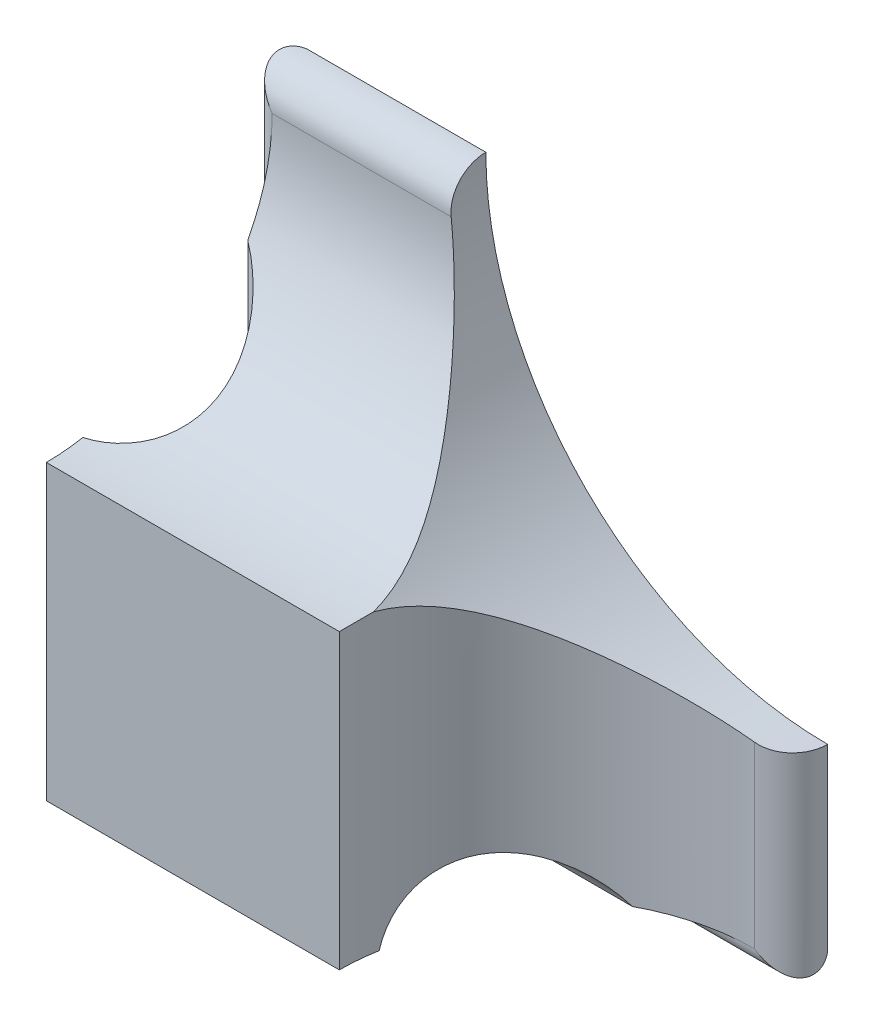
SolidWorks part; units mm, degrees
material "Золото без примесей"
ref_plane "Front" through (0, 0, 0) normal (0, 0, 1) x (1, 0, 0)
ref_plane "Top" through (0, 0, 0) normal (0, 1, 0) x (1, 0, 0)
ref_plane "Right" through (0, 0, 0) normal (1, 0, 0) x (0, 0, -1)
sketch "Эскиз1" plane through (0, 0, 0) normal (0, 0, 1) x (1, 0, 0)
  line L0 (0, 0) -> (22, 0)
  line L1 (22, 0) -> (22, 8)
  line L2 (0, 0) -> (19.7111, 19.7111) construction
  line L4 (12.1005, 12.1005) -> (0, 0)
  line L5 (22, 8) -> (22.8779, 8) construction
  line L6 (12.1005, 12.1005) -> (8.2773, 15.9237) construction
  arc A0 (22, 8) -> (12.1005, 12.1005) centre (22, 22) cw
  dimension "D1" = 45
  dimension "D2" = 8
  dimension "D3" = 22
extrude "Основная форма" add sketch "Эскиз1" along normal blind 10
sketch "Эскиз2" plane through (22, 0, 0) normal (1, 0, 0) x (0, 0, -1)
  line L1 (-10, -1) -> (0, -1)
  line L2 (0, 0.75) -> (0, -1)
  line L5 (-10, 0) -> (0, 0) construction
  line L6 (-10, 0) -> (-10, -1)
  line L8 (-10, 0) -> (-8.5, 0)
  line L10 (-1.5, 0.75) -> (-2.5, 0.75)
  line L11 (0, 0) -> (0, 8) construction
  line L12 (-10.4143, 2.5) -> (-4.9819, 2.5) construction
  arc A3 (-8.5, 0) -> (-2.5, 0.75) centre (-5.3634, -0.7176) cw
  arc A4 (0, 0.75) -> (-1.5, 0.75) centre (-0.75, 0.75) cw
  dimension "D1" = 2.5
  dimension "D2" = 1
  dimension "D3" = 1.5
  dimension "D5" = 1
  dimension "D7" = 1.5
extrude "Вырез фигурный, фронт" cut sketch "Эскиз2" against normal through all
sketch "Эскиз3" plane through (0, 0, 0) normal (0, 1, 0) x (1, 0, 0)
  line L4 (22, 0) -> (22, -10)
  line L6 (22, -10) -> (12, -10)
  line L9 (0, -10) -> (22, -10) construction
  line L10 (0.75, -1.5) -> (22, -1.5) construction
  line L11 (20.5, -10) -> (20.5, -1.5) construction
  arc A4 (12, -10) -> (20.5, -1.5) centre (20.5, -10) cw
  arc A5 (20.5, -1.5) -> (22, 0) centre (20.5, 0) ccw
extrude "Вырез фигурный, бок" cut sketch "Эскиз3" along normal through all
sketch "Эскиз5" plane through (0, 0, 0) normal (0, 0, -1) x (-1, 0, 0)
  line L1 (-8.75, 4.75) -> (-4.75, 4.75) construction
  line L6 (-12.1005, 12.1005) -> (-0.75, 0.75) construction
  line L7 (-22, 0.75) -> (-0.75, 0.75) construction
  line L8 (-5.9216, 5.9216) -> (-2.2649, 9.5783) construction
  line L9 (-12, 12) -> (-12.1005, 12.1005) construction
  line L10 (-8.75, 4.75) -> (-12.75, 4.75)
  arc A0 (-5.9216, 5.9216) -> (-8.75, 4.75) centre (-8.75, 8.75) cw
  dimension "D2" = 4
  dimension "D1" = 4
  dimension "D3" = 8
extrude "Вырез под финсатор" cut sketch "Эскиз5" against normal blind 3 and the other way through all thin thin type mid plane wall 1.4
mirror "Зеркальное отражение1" about plane through (12.1005, 12.1005, 10) normal (0.7071, -0.7071, 0) of "Вырез под финсатор", "Вырез фигурный, фронт", "Вырез фигурный, бок", "Основная форма"
chamfer "Фаска1" distance 0.5 angle 45 8 edges at (12.75, 4.75, 0) (10.75, 5.45, 0) (6.4165, 6.4165, 0) (10.75, 4.05, 0) (5.4266, 5.4266, 0) (5.45, 10.75, 0) (4.05, 10.75, 0) (4.75, 12.75, 0)
